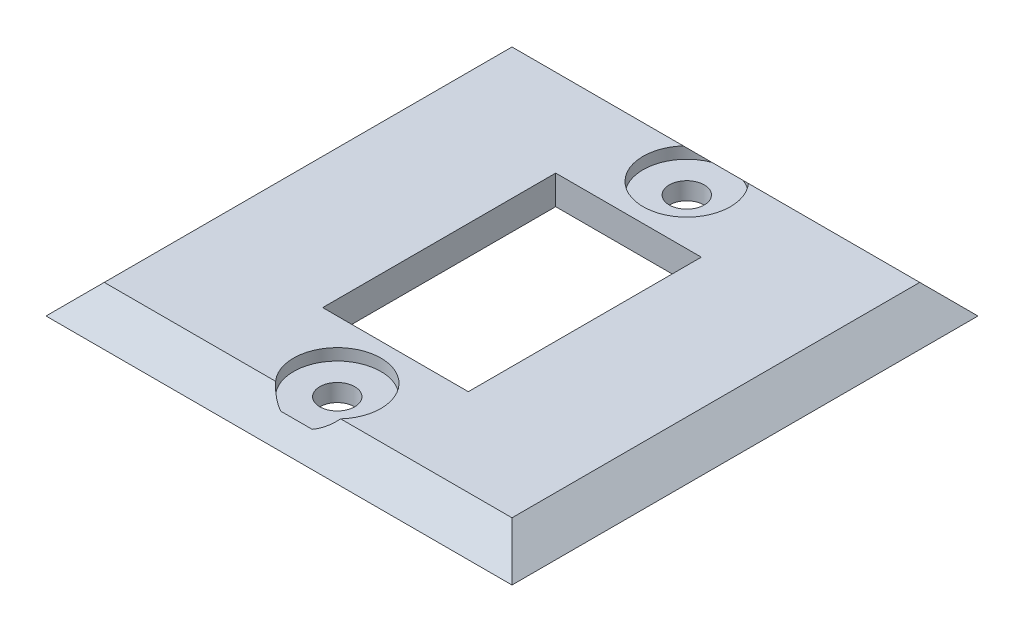
SolidWorks part; units mm, degrees
ref_plane "Front Plane" through (0, 0, 0) normal (0, 0, 1) x (1, 0, 0)
ref_plane "Top Plane" through (0, 0, 0) normal (0, 1, 0) x (1, 0, 0)
ref_plane "Right Plane" through (0, 0, 0) normal (1, 0, 0) x (0, 0, -1)
sketch "Sketch1" plane through (0, 0, 0) normal (0, 1, 0) x (1, 0, 0)
  line L0 (-20, 20) -> (20, -20) construction
  line L1 (-20, 20) -> (20, 20)
  line L2 (-20, 20) -> (-20, -20)
  line L3 (-20, -20) -> (20, -20)
  line L4 (20, 20) -> (20, -20)
  line L5 (-6.25, 10) -> (6.25, 10)
  line L6 (-6.25, 10) -> (-6.25, -10)
  line L7 (-6.25, -10) -> (6.25, -10)
  line L8 (6.25, 10) -> (6.25, -10)
  line L9 (6.25, 10) -> (-6.25, -10) construction
  point P8 (0, 0)
  point P9 (0, 0)
  dimension "D1" = 40
  dimension "D2" = 12.5
  dimension "D3" = 20
  dimension "D4" = 40
extrude "Boss-Extrude1" add sketch "Sketch1" along normal blind 2.5
sketch "Sketch2" plane through (0, 2.5, 0) normal (0, 1, 0) x (1, 0, 0)
  line L0 (0, 0) -> (0, -7.7634) construction
  line L1 (-6.25, 10) -> (0, 15) construction
  line L2 (0, 15) -> (6.25, 10) construction
  line L3 (-6.25, -20) -> (0, -15) construction
  line L4 (0, -15) -> (6.25, -10) construction
  line L5 (-20, -20) -> (20, -20) construction
  line L6 (-6.25, 10) -> (-6.25, -10) construction
  line L7 (-6.25, -10) -> (0, -15) construction
  line L8 (0, 13.5) -> (-12.7123, 13.5) construction
  line L10 (-13.9598, -13.5) -> (13.5617, -13.5) construction
  circle A0 centre (0, 15) radius 1.5
  circle A1 centre (0, -15) radius 1.5
  dimension "D1" = 3
  dimension "D2" = 27
extrude "Cut-Extrude1" cut sketch "Sketch2" against normal blind 10
sketch "Sketch3" plane through (0, 2.5, 0) normal (0, 1, 0) x (1, 0, 0)
  circle A0 centre (0, 15) radius 3.75
  circle A1 centre (0, -15) radius 3.75
  point P6 (0, -14.75)
  dimension "D1" = 7.5
extrude "Cut-Extrude2" cut sketch "Sketch3" against normal blind 1
chamfer "Chamfer1" distance 2.5 angle 45 4 edges at (20, 2.5, 0) (0, 2.5, 20) (0, 2.5, -20) (-20, 2.5, 0)
